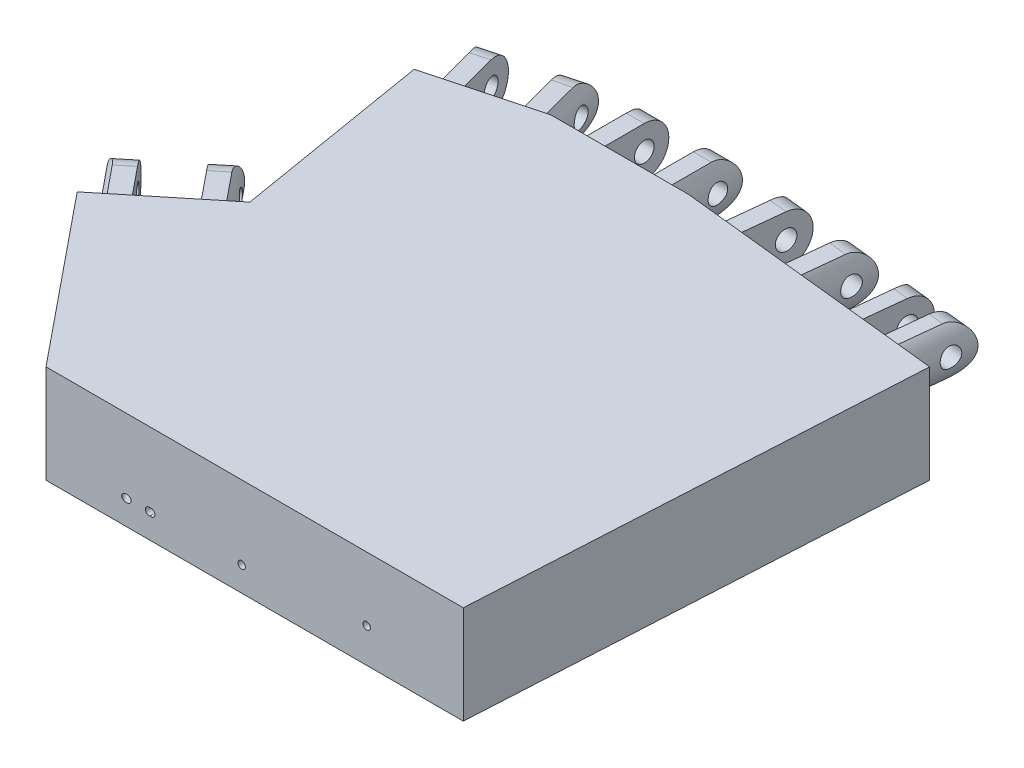
SolidWorks part; units mm, degrees
note: The reader was unsure of these and kept them because the rebuilt part matched: shared geometry of "Sketch2<3>", "Sketch4<4>", "Sketch7<4>", "Sketch10<6>".
ref_plane "Front Plane" through (0, 0, 0) normal (0, 0, 1) x (1, 0, 0)
ref_plane "Top Plane" through (0, 0, 0) normal (0, 1, 0) x (1, 0, 0)
ref_plane "Right Plane" through (0, 0, 0) normal (1, 0, 0) x (0, 0, -1)
sketch "Sketch1" plane through (0, 0, 0) normal (0, 1, 0) x (1, 0, 0)
  line L0 (-52.5, 45) -> (-22.5, 53)
  line L1 (52.5, -45) -> (-52.5, -45)
  line L2 (52.5, -45) -> (52.5, 45)
  line L3 (52.5, 45) -> (-52.5, 45)
  line L4 (-52.5, -45) -> (-52.5, 45)
  line L5 (0, 45) -> (0, -45) construction
  line L6 (52.5, 0) -> (-52.5, 0) construction
  line L7 (-22.5, 53) -> (52.5, 45)
  line L8 (-52.5, 45) -> (-37.5, -45)
  line L9 (52.5, 45) -> (47.5, -45)
  line L10 (-2.5, 50.8667) -> (-30.5, 50.8667)
  point P0 (0, 0)
  dimension "D1" = 105
  dimension "D2" = 90
  dimension "D3" = 8
  dimension "D4" = 30
  dimension "D5" = 5
  dimension "D6" = 15
  dimension "D7" = 8
extrude "Boss-Extrude1" add sketch "Sketch1" along normal blind 20 contours L4 L1 L2 L3 | L7 L0 L3
sketch "Sketch2" plane through (-14.6888, 0, -55.083) normal (-0.2577, 0, -0.9662) x (-0.9662, 0, 0.2577)
  line L0 (39.1325, 20) -> (39.1325, 0) construction
  line L1 (22.1325, 21.6603) -> (22.1325, 4.3397)
  line L2 (39.1325, 20) -> (16.3637, 20) construction
  line L4 (32.1325, 21.6603) -> (32.1325, 4.3397)
  line L5 (18.4723, 8) -> (35.7928, 8)
  line L6 (18.4723, 8) -> (18.4723, 18)
  line L7 (18.4723, 18) -> (35.7928, 18)
  line L8 (35.7928, 8) -> (35.7928, 18)
  line L9 (27.1325, 18) -> (27.1325, 8) construction
  line L10 (18.4723, 13) -> (35.7928, 13) construction
  circle A0 centre (27.1325, 13) radius 10
  circle A1 centre (27.1325, 5) radius 0.75
  point P18 (27.1325, 3)
  dimension "D1" = 20
  dimension "D6" = 1.5
  dimension "D7" = 2
  dimension "D2" = 12
  dimension "D3" = 10
  dimension "D4" = 5
  dimension "D5" = 7
extrude "Boss-Extrude2" add sketch "Sketch2" along normal blind 15 contours L7 L6 L5 L1 | L6 A0 | L5 L8 L7 L4 | L8 A0
sketch "Sketch4" plane through (5.3366, 0, -50.0308) normal (0.1061, 0, -0.9944) x (-0.9944, 0, -0.1061)
  line L1 (7.8811, 20) -> (-47.4309, 20) construction
  line L4 (7.8811, 20) -> (7.8811, 0) construction
  line L12 (-12.1189, 21.6603) -> (-12.1189, 4.3397)
  line L13 (-2.1189, 21.6603) -> (-2.1189, 4.3397)
  line L14 (-15.7792, 8) -> (1.5413, 8)
  line L15 (-15.7792, 8) -> (-15.7792, 18)
  line L16 (-15.7792, 18) -> (1.5413, 18)
  line L17 (1.5413, 8) -> (1.5413, 18)
  line L18 (-7.1189, 18) -> (-7.1189, 8) construction
  line L19 (-15.7792, 13) -> (1.5413, 13) construction
  line L20 (-34.9309, 20.0711) -> (-34.9309, 5.9289)
  line L21 (-29.9309, 20.0711) -> (-29.9309, 5.9289)
  line L22 (-38.0211, 8) -> (-26.8408, 8)
  line L23 (-38.0211, 8) -> (-38.0211, 18)
  line L24 (-38.0211, 18) -> (-26.8408, 18)
  line L25 (-26.8408, 8) -> (-26.8408, 18)
  line L26 (-32.4309, 18) -> (-32.4309, 8) construction
  line L27 (-38.0211, 13) -> (-26.8408, 13) construction
  line L28 (-47.4309, 20) -> (-47.4309, 0) construction
  circle A1 centre (-7.1189, 13) radius 10
  circle A2 centre (-32.4309, 13) radius 7.5
  circle A3 centre (-7.1189, 5) radius 0.75
  circle A4 centre (-32.4309, 7) radius 0.75
  point P2 (-24.9309, 13)
  point P5 (-7.1189, 3)
  point P6 (-32.4309, 5.5)
  dimension "D6" = 20
  dimension "D10" = 15
  dimension "D7" = 1.5
  dimension "D9" = 1.5
  dimension "D14" = 1.5
  dimension "D2" = 7
  dimension "D3" = 15
  dimension "D4" = 10
  dimension "D5" = 5
  dimension "D8" = 5
  dimension "D11" = 10
  dimension "D12" = 2
  dimension "D13" = 15
sketch "Sketch3" plane through (-31.0476, 0, 8.2793) normal (0.9662, 0, -0.2577) x (-0.2577, 0, -0.9662)
  line L0 (72.0079, 18) -> (57.0079, 18) construction
  line L1 (72.0079, 8) -> (57.0079, 8) construction
  line L2 (72.0079, 8) -> (72.0079, 18) construction
  arc A0 (67.0079, 18) -> (67.0079, 8) centre (67.0079, 13) cw
  circle A1 centre (67.0079, 13) radius 2
  line M2 (57.0079, 8) -> (72.0079, 8)
  line M3 (72.0079, 8) -> (72.0079, 18)
  line M4 (72.0079, 18) -> (57.0079, 18)
  dimension "D1" = 4
extrude "Cut-Extrude1" cut sketch "Sketch3" against normal through all both and the other way through all contours A0 M4 M3 | A0 M3 M2 | A1
sketch "Sketch7" plane through (0, 0, -50.8667) normal (0, 0, -1) x (-1, 0, 0)
  line L0 (11.5, 21.6603) -> (11.5, 4.3397)
  line L1 (21.5, 21.6603) -> (21.5, 4.3397)
  line L2 (7.8397, 8) -> (25.1603, 8)
  line L3 (7.8397, 8) -> (7.8397, 18)
  line L4 (7.8397, 18) -> (25.1603, 18)
  line L5 (25.1603, 8) -> (25.1603, 18)
  line L6 (16.5, 18) -> (16.5, 8) construction
  line L7 (7.8397, 13) -> (25.1603, 13) construction
  line L8 (2.5, 20) -> (30.5, 20) construction
  line L9 (30.5, 20) -> (30.5, 0) construction
  circle A0 centre (16.5, 13) radius 10
  circle A1 centre (16.5, 5) radius 0.75
  point P20 (16.5, 3)
  dimension "D1" = 20
  dimension "D5" = 14
  dimension "D6" = 1.5
  dimension "D2" = 5
  dimension "D3" = 10
  dimension "D4" = 7
  dimension "D7" = 2
extrude "Boss-Extrude4" add sketch "Sketch7" along normal blind 15 contours L2 L5 L4 L1 | L4 L3 L2 L0 | L3 A0 | L5 A0
sketch "Sketch8" plane through (-21.5, 0, 0) normal (1, 0, 0) x (0, 0, -1)
  line L3 (65.8667, 18) -> (50.8667, 18) construction
  line L4 (65.8667, 18) -> (65.8667, 8) construction
  line L6 (65.8667, 8) -> (50.8667, 8) construction
  arc A0 (60.8667, 18) -> (60.8667, 8) centre (60.8667, 13) cw
  circle A1 centre (60.8667, 13) radius 2
  line M16 (50.8667, 8) -> (65.8667, 8)
  line M17 (65.8667, 8) -> (65.8667, 18)
  line M18 (65.8667, 18) -> (50.8667, 18)
  dimension "D1" = 4
extrude "Cut-Extrude4" cut sketch "Sketch8" along normal up to surface and the other way up to surface contours A0 M18 M17 | A0 M17 M16 | A1 up to face at (-25.8301, 13, -58.3667) other way up to face at (-25.8301, 13, -58.3667)
extrude "Boss-Extrude3" add sketch "Sketch4" along normal blind 15 contours L17 A1 | L14 L17 L16 L13 | L16 L15 L14 L12 | L15 A1 | L22 L25 L24 L21 | L25 A2 | L24 L23 L22 L20 | L23 A2
sketch "Sketch6" plane through (2.107, 0, 0.2247) normal (0.9944, 0, 0.1061) x (0.1061, 0, -0.9944)
  line L0 (65.3146, 18) -> (50.3146, 18) construction
  line L1 (65.3146, 8) -> (50.3146, 8) construction
  line L2 (65.3146, 8) -> (65.3146, 18) construction
  arc A0 (60.3146, 18) -> (60.3146, 8) centre (60.3146, 13) cw
  circle A1 centre (60.3146, 13) radius 2
  dimension "D1" = 4
extrude "Cut-Extrude3" cut sketch "Sketch6" against normal up to surface and the other way up to surface
extrude "Cut-Extrude5" cut sketch "Sketch2<3>" against normal through all contours A1
sketch "Sketch2<3>" plane through (-14.6888, 0, -55.083) normal (-0.2577, 0, -0.9662) x (-0.9662, 0, 0.2577) same geometry as "Sketch2"
extrude "Cut-Extrude6" cut sketch "Sketch4<4>" against normal through all contours A4 | A3
sketch "Sketch4<4>" plane through (5.3366, 0, -50.0308) normal (0.1061, 0, -0.9944) x (-0.9944, 0, -0.1061) same geometry as "Sketch4"
extrude "Cut-Extrude7" cut sketch "Sketch7<4>" against normal through all contours A1
sketch "Sketch7<4>" plane through (0, 0, -50.8667) normal (0, 0, -1) x (-1, 0, 0) same geometry as "Sketch7"
sketch "Sketch9" plane through (0, 20, 0) normal (0, 1, 0) x (1, 0, 0)
  line L0 (-45.8044, 4.8266) -> (-65.1983, -10.9492)
  line L1 (-52.5, 45) -> (-37.5, -45) construction
  line L2 (-65.1983, -10.9492) -> (-37.5, -45)
  line L9 (47.5, -45) -> (52.5, 45)
  line L10 (52.5, 45) -> (-2.5, 50.8667)
  line L11 (-2.5, 50.8667) -> (-30.5, 50.8667)
  line L12 (-30.5, 50.8667) -> (-52.5, 45)
  line L13 (-52.5, 45) -> (-37.5, -45)
  line L14 (-37.5, -45) -> (47.5, -45)
  line L19 (-45.8044, 4.8266) -> (-37.5, -45)
  point P4 (-37.5, -45)
  point P6 (-46.1169, 6.7016)
  dimension "D1" = 25
  dimension "D2" = 43.8937
  dimension "D3" = 0
extrude "Boss-Extrude5" add sketch "Sketch9" against normal up to surface (20 mm away) up to face at (-3.8333, 0, -16.9556)
sketch "Sketch10" plane through (-20.6022, 0, -25.3272) normal (-0.631, 0, -0.7758) x (-0.7758, 0, 0.631)
  line L0 (39.7797, 21.6603) -> (39.7797, 4.3397)
  line L1 (49.7797, 21.6603) -> (49.7797, 4.3397)
  line L2 (36.1195, 8) -> (53.44, 8)
  line L3 (36.1195, 8) -> (36.1195, 18)
  line L4 (36.1195, 18) -> (53.44, 18)
  line L5 (53.44, 8) -> (53.44, 18)
  line L6 (44.7797, 18) -> (44.7797, 8) construction
  line L7 (36.1195, 13) -> (53.44, 13) construction
  line L11 (32.4873, 20) -> (57.4873, 20) construction
  circle A0 centre (44.7797, 13) radius 10
  circle A1 centre (44.7797, 5) radius 0.75
  point P15 (44.7797, 9.3541)
  point P16 (44.7797, -2.2335)
  point P17 (0, 0)
  point P18 (43.2502, -0.721)
  point P20 (44.7797, 3)
  point P23 (43.2502, -0.721)
  dimension "D1" = 20
  dimension "D6" = 1.5
  dimension "D2" = 5
  dimension "D3" = 10
  dimension "D4" = 7
  dimension "D7" = 2
extrude "Boss-Extrude6" add sketch "Sketch10" along normal blind 15 contours L4 L3 L2 L0 | L3 A0 | L5 A0 | L2 L5 L4 L1
sketch "Sketch11" plane through (-38.617, 0, 31.4126) normal (0.7758, 0, -0.631) x (-0.631, 0, -0.7758)
  line L0 (47.6484, 8) -> (32.6484, 8) construction
  line L1 (47.6484, 18) -> (32.6484, 18) construction
  line L2 (47.6484, 18) -> (47.6484, 8) construction
  arc A0 (42.6484, 18) -> (42.6484, 8) centre (42.6484, 13) cw
  circle A1 centre (42.6484, 13) radius 2
  point P3 (41.9229, 12.5722)
  point P4 (0, 0)
  point P7 (0, 0)
  line M23 (32.6484, 8) -> (47.6484, 8)
  line M24 (47.6484, 8) -> (47.6484, 18)
  line M25 (47.6484, 18) -> (32.6484, 18)
  dimension "D1" = 4
extrude "Cut-Extrude8" cut sketch "Sketch11" against normal up to surface (7.7076 mm away) and the other way up to surface contours A0 M25 M24 | A0 M24 M23 | A1 other way up to face at (-52.8352, 13, -8.7755)
extrude "Cut-Extrude9" cut sketch "Sketch10<6>" against normal through all contours A1
sketch "Sketch10<6>" plane through (-20.6022, 0, -25.3272) normal (-0.631, 0, -0.7758) x (-0.7758, 0, 0.631) same geometry as "Sketch10"
chamfer "Chamfer1" distance 2 angle 45 5 edges at (-41.6299, 5, -47.8987) (-17.25, 5, -50.8667) (36.8388, 7, -46.6705) (11.6696, 5, -49.3552) (-55.9222, 5, 3.4036)
